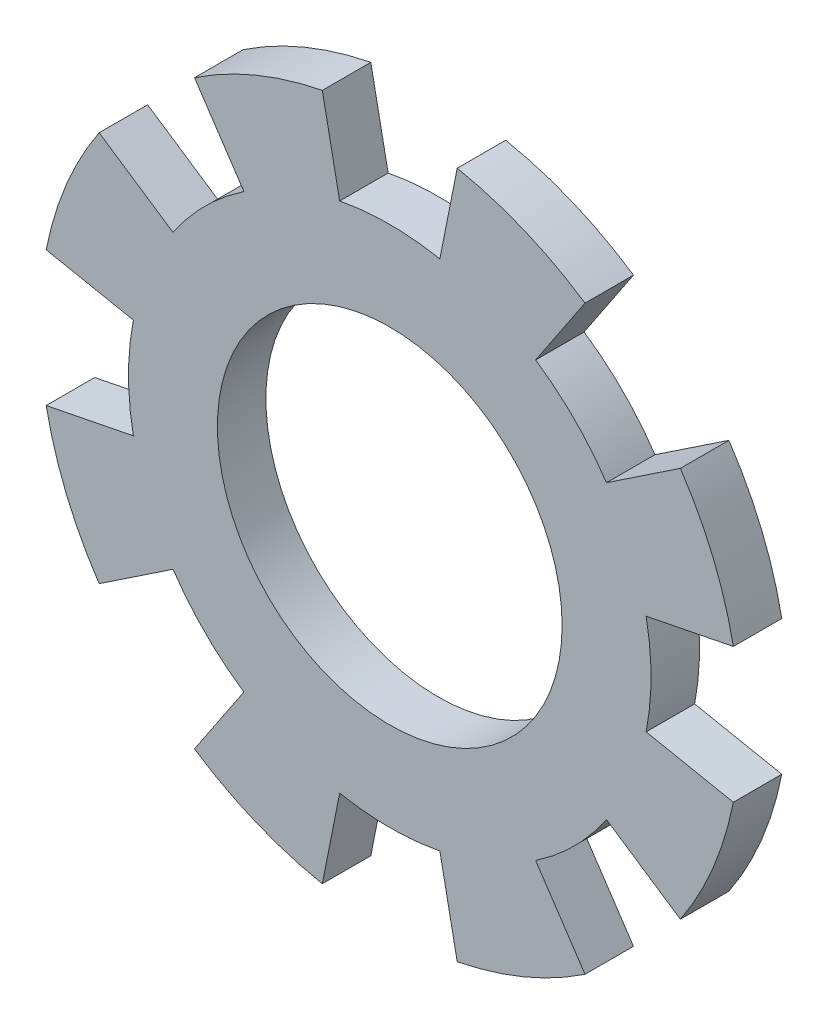
SolidWorks part; units mm, degrees
ref_plane "Front Plane" through (0, 0, 0) normal (0, 0, 1) x (1, 0, 0)
ref_plane "Top Plane" through (0, 0, 0) normal (0, 1, 0) x (1, 0, 0)
ref_plane "Right Plane" through (0, 0, 0) normal (1, 0, 0) x (0, 0, -1)
sketch "BodySke" plane through (0, 0, 0) normal (0, 1, 0) x (1, 0, 0)
  line L0 (0, 0) -> (0, 8) construction
  line L2 (1.6, 0) -> (3.25, 0)
  line L3 (1.6, 0) -> (1.6, 0.45)
  line L4 (1.6, 0.45) -> (3.25, 0.45)
  line L5 (3.25, 0) -> (3.25, 0.45)
revolve "BaseBody" add sketch "BodySke" angle 360 about L0
sketch "ToothSke" plane through (0, 0, 0) normal (0, 0, 1) x (1, 0, 0)
  line L0 (0, 0) -> (0, 2.7341) construction
  line L2 (-0.4651, 2.38) -> (-0.6381, 3.25)
  line L3 (0.6381, 3.25) -> (-0.6381, 3.25)
  line L4 (0.4651, 2.38) -> (0.6381, 3.25)
  circle A0 centre (0, 0) radius 2.425 construction
  arc A1 (-0.4651, 2.38) -> (0.4651, 2.38) centre (0, 0) cw
  circle A2 centre (0, 0) radius 1.6 construction
  circle A3 centre (0, 0) radius 1.6 construction
  circle A4 centre (0, 0) radius 3.25 construction
  point P11 (0, 1.083)
  point P12 (0, 2.425)
  point P15 (0, 2.4103)
  point P16 (0, 3.25)
  dimension "D1" = 4.85
  dimension "D2" = 1.2763
  dimension "D3" = 22.5
extrude "ToothCut" cut sketch "ToothSke" against normal through all
pattern_circular "ToothPat" count 8 over 360 about axis through (0, 0, 0) along (0, 0, -1) of "ToothCut"
equation "\"D1@ToothSke\" =  ( \"Inner_dia@BodySke\" + \"Outer_dia@BodySke\" )  / 2"
equation "\"D2@ToothSke\" =  pi  * \"Outer_dia@BodySke\" / 2 / \"Num_tooth@BodySke\""
equation "\"D3@ToothSke\" = 360 / 2 / \"Num_tooth@BodySke\" "
equation "\"Num_tooth@ToothPat\" = \"Num_tooth@BodySke\""
